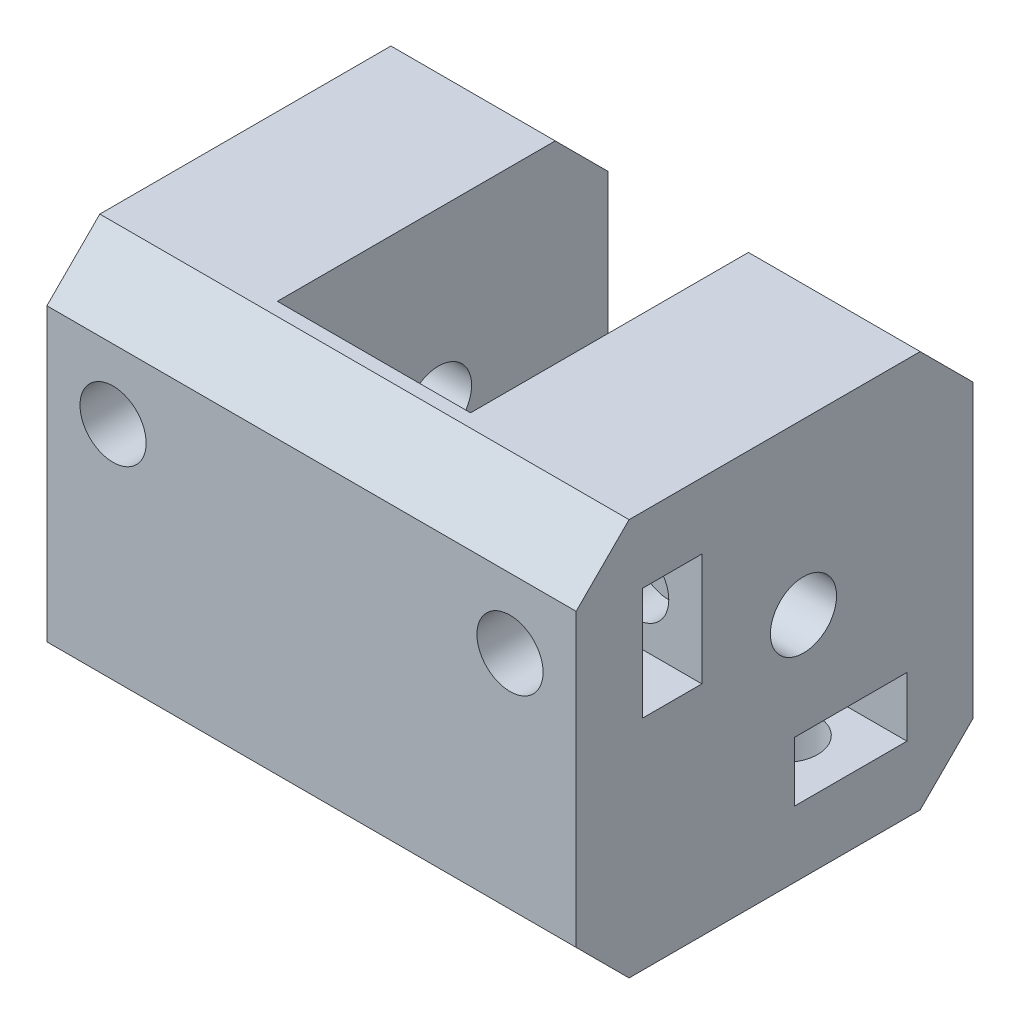
SolidWorks part; units mm, degrees
ref_plane "Front Plane" through (0, 0, 0) normal (0, 0, 1) x (1, 0, 0)
ref_plane "Top Plane" through (0, 0, 0) normal (0, 1, 0) x (1, 0, 0)
ref_plane "Right Plane" through (0, 0, 0) normal (1, 0, 0) x (0, 0, -1)
sketch "Sketch1" plane through (0, 0, 0) normal (0, 0, 1) x (1, 0, 0)
  line L0 (-71.5929, 28.752) -> (-71.5929, 34.452) construction
  line L1 (-31.5929, 27.752) -> (-71.5929, 27.752)
  line L2 (-31.5929, 27.752) -> (-31.5929, 57.752)
  line L3 (-31.5929, 57.752) -> (-71.5929, 57.752)
  line L4 (-71.5929, 27.752) -> (-71.5929, 57.752)
  line L5 (-64.8929, 27.752) -> (-70.5929, 27.752) construction
  line L6 (-31.5929, 34.452) -> (-31.5929, 28.752) construction
  dimension "D1" = 30
extrude "Boss-Extrude1" add sketch "Sketch1" along normal blind 30 contours L3 L4 L1 L2
sketch "Sketch2" plane through (0, 57.752, 0) normal (0, 1, 0) x (1, 0, 0)
  line L0 (-31.5929, 0) -> (-71.5929, 0) construction
  line L1 (-44.5729, -25) -> (-59.1729, -25)
  line L2 (-44.5729, -25) -> (-44.5729, 8.7289)
  line L3 (-44.5729, 8.7289) -> (-59.1729, 8.7289)
  line L4 (-59.1729, -25) -> (-59.1729, 8.7289)
  line L5 (-45.5729, -15.5089) -> (-45.5729, -10.5089) construction
  line L6 (-45.5729, -15.5089) -> (-45.5729, -10.5089) construction
  line L7 (-58.1729, -6.0089) -> (-58.1729, -20.0089) construction
  line L8 (-58.1729, -6.0089) -> (-58.1729, -20.0089) construction
  dimension "D1" = 25
  dimension "D2" = 1
  dimension "D3" = 1
extrude "Cut-Extrude1" cut sketch "Sketch2" against normal offset from surface (25 mm away) 5 up to face at (-51.5929, 27.752, 15)
sketch "Sketch3" plane through (-31.5929, 0, 0) normal (1, 0, 0) x (0, 0, -1)
  line L0 (0, 57.752) -> (-30, 27.752) construction
  line L1 (-30, 57.752) -> (0, 57.752) construction
  line L2 (0, 27.752) -> (0, 57.752) construction
  circle A1 centre (-12.8221, 44.9299) radius 2.5 construction
  circle A2 centre (-12.8221, 44.9299) radius 2.5
  dimension "D1" = 5
extrude "Cut-Extrude2" cut sketch "Sketch3" against normal through all contours A2
sketch "Sketch4" plane through (-31.5929, 0, 0) normal (1, 0, 0) x (0, 0, -1)
  line L0 (0, 57.752) -> (-30, 27.752) construction
  line L1 (-5, 32.752) -> (-13.5, 32.752)
  line L2 (-5, 32.752) -> (-5, 37.252)
  line L3 (-5, 37.252) -> (-13.5, 37.252)
  line L4 (-13.5, 32.752) -> (-13.5, 37.252)
  line L5 (-25, 52.752) -> (-25, 44.252)
  line L6 (-25, 52.752) -> (-20.5, 52.752)
  line L7 (-20.5, 52.752) -> (-20.5, 44.252)
  line L8 (-25, 44.252) -> (-20.5, 44.252)
  line L9 (0, 27.752) -> (0, 57.752) construction
  line L10 (-30, 27.752) -> (0, 27.752) construction
  dimension "D1" = 8.5
  dimension "D2" = 4.5
  dimension "D3" = 5
  dimension "D4" = 5
extrude "Cut-Extrude3" cut sketch "Sketch4" against normal blind 9
extrude "Cut-Extrude4" cut sketch "Sketch4<2>" along normal blind 9 from surface starting at face at (-71.5929, 44.9299, 10.3221)
sketch "Sketch4<2>" plane through (-31.5929, 0, 0) normal (1, 0, 0) x (0, 0, -1) same geometry as "Sketch4"
sketch "Sketch5" plane through (0, 0, 30) normal (0, 0, 1) x (1, 0, 0)
  line L0 (-62.5929, 44.252) -> (-62.5929, 52.752) construction
  line L1 (-40.5929, 52.752) -> (-40.5929, 44.252) construction
  line L2 (-62.5929, 44.252) -> (-62.5929, 52.752) construction
  line L3 (-40.5929, 52.752) -> (-40.5929, 44.252) construction
  line L4 (-66.5929, 48.502) -> (-36.5929, 48.502) construction
  circle A0 centre (-66.5929, 48.502) radius 2.5
  circle A1 centre (-36.5929, 48.502) radius 2.5
  point P8 (-62.5929, 48.502)
  dimension "D3" = 5
  dimension "D1" = 4
  dimension "D2" = 4
extrude "Cut-Extrude5" cut sketch "Sketch5" against normal blind 12
ref_plane "Plane1" through (0, 28.876, 28.876) normal (0, -0.7071, -0.7071) x (-1, 0, 0)
mirror "Mirror1" about plane through (0, 28.876, 28.876) normal (0, -0.7071, -0.7071) of "Cut-Extrude5"
chamfer "Chamfer1" distance 4 angle 45 5 edges at (-51.5929, 57.752, 30) (-65.3829, 57.752, 0) (-38.0829, 57.752, 0) (-51.5929, 27.752, 0) (-51.5929, 27.752, 30)
